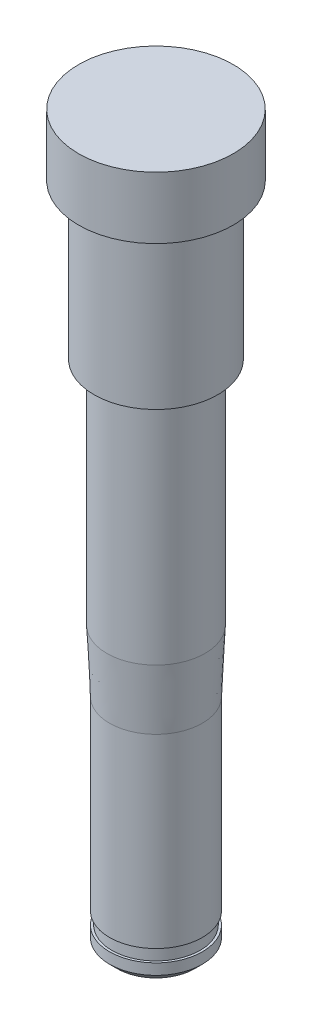
SolidWorks part; units mm, degrees
ref_plane "Front Plane" through (0, 0, 0) normal (0, 0, 1) x (1, 0, 0)
ref_plane "Top Plane" through (0, 0, 0) normal (0, 1, 0) x (1, 0, 0)
ref_plane "Right Plane" through (0, 0, 0) normal (1, 0, 0) x (0, 0, -1)
ref_axis "X-Axis" through (-88.99, 0, 0) along (1, 0, 0)
ref_axis "Y-Axis" through (0, 55, 0) along (0, -1, 0)
ref_axis "Z-Axis" through (0, 0, 55) along (0, 0, -1)
sketch "Sketch1" plane through (0, 0, 0) normal (0, 0, 1) x (1, 0, 0)
  line L0 (0, 55) -> (0, -55) construction
  line L1 (0, -16.9) -> (-3.175, -16.9)
  line L4 (-3.175, -16.9) -> (-3.175, 16)
  line L5 (-88.99, 0) -> (88.99, 0) construction
  line L6 (-3.175, 16) -> (-4, 16)
  line L7 (0, -16.9) -> (0, 18.8253)
  line L9 (-4, 16) -> (-4, 26)
  line L10 (-4, 26) -> (-5, 26)
  line L11 (0, 18.8253) -> (0, 30)
  line L12 (0, 30) -> (-5, 30)
  line L13 (-5, 26) -> (-5, 30)
  dimension "D1" = 3.175
  dimension "D2" = 4
  dimension "D3" = 5
  dimension "D4" = 46.9
  dimension "D5" = 10
  dimension "D6" = 4
  dimension "D7" = 30
revolve "Revolve1" add sketch "Sketch1" angle 360 about axis through (0, 55, 0) along (0, -1, 0)
sketch "Sketch2" plane through (0, 0, 0) normal (0, 0, 1) x (1, 0, 0)
  line L0 (-3, -2.9) -> (-3.175, 1.1)
  line L1 (-3.175, -16.9) -> (-3, -16.9)
  line L2 (-3.175, -16.9) -> (-3.175, -3.6989)
  line L4 (-3, -16.9) -> (-3, -2.9)
  line L5 (-3.175, 16) -> (-3.175, -16.9) construction
  line L6 (-3.175, -3.6989) -> (-3.175, 1.1)
  point P5 (0, 0)
  point P9 (-3, -3.2719)
  dimension "D1" = 3
  dimension "D2" = 18
  dimension "D3" = 4
revolve "Cut-Revolve1" cut sketch "Sketch2" angle 360 about axis through (0, 55, 0) along (0, -1, 0)
chamfer "Chamfer5" distance 0.5 angle 45 1 edges at (0, -16.9, 3)
sketch "Sketch3" plane through (0, 0, 0) normal (1, 0, 0) x (0, 0, -1)
  line L0 (3, -16.4) -> (3, -2.9) construction
  line L1 (3, -15.7) -> (2.85, -15.7)
  line L2 (3, -15.7) -> (3, -14.9)
  line L3 (3, -14.9) -> (2.85, -14.9)
  line L4 (2.85, -15.7) -> (2.85, -14.9)
  line L5 (3, -16.4) -> (-3, -16.4) construction
  line L6 (0, 55) -> (0, -55) construction
  dimension "D1" = 0.7
  dimension "D2" = 0.8
  dimension "D3" = 2.85
revolve "Cut-Revolve2" cut sketch "Sketch3" angle 360 about axis through (0, 55, 0) along (0, -1, 0)
